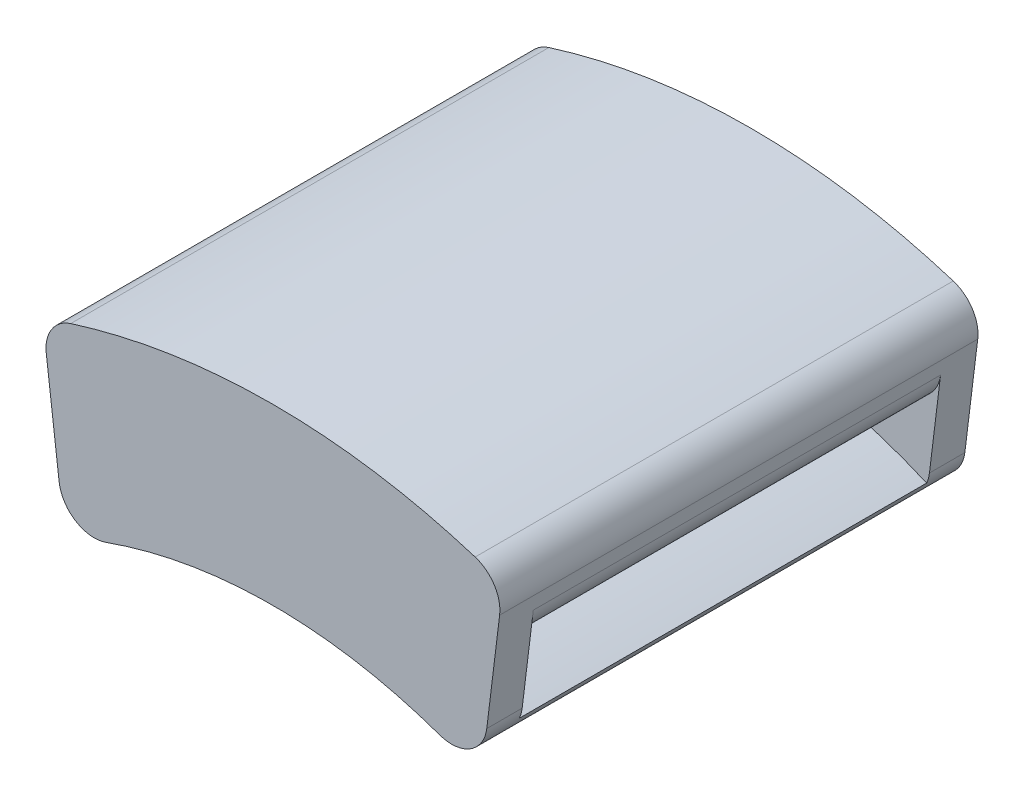
SolidWorks part; units mm, degrees
ref_plane "Front Plane" through (0, 0, 0) normal (0, 0, 1) x (1, 0, 0)
ref_plane "Top Plane" through (0, 0, 0) normal (0, 1, 0) x (1, 0, 0)
ref_plane "Right Plane" through (0, 0, 0) normal (1, 0, 0) x (0, 0, -1)
sketch "Sketch1" plane through (0, 0, 0) normal (0, 0, 1) x (1, 0, 0)
  line L0 (13.1474, 36.827) -> (12.2845, 29.8088) construction
  line L1 (-13.1588, 36.9193) -> (-12.2958, 29.9011) construction
  line L2 (-13, 35.628) -> (-12.3966, 30.7212)
  line L3 (13, 35.628) -> (12.3966, 30.7212)
  line L4 (11.7559, 25.5104) -> (12, 27.4955)
  line L5 (-10, 35.628) -> (10, 35.628) construction
  line L6 (-10, 35.628) -> (-10, 33.128) construction
  line L7 (-10, 33.128) -> (10, 33.128) construction
  line L8 (10, 35.628) -> (10, 33.128) construction
  line L9 (-11.7559, 25.5104) -> (-12, 27.4955)
  circle A0 centre (0, 0) radius 30 construction
  arc A1 (-12, 27.4955) -> (12, 27.4955) centre (0, 0) cw
  arc A2 (-13, 35.628) -> (13, 35.628) centre (0, 0) cw
  arc A3 (-12.3966, 30.7212) -> (12.3966, 30.7212) centre (0, 0) cw
  arc A4 (-11.7559, 25.5104) -> (11.7559, 25.5104) centre (0, 0) cw
  point P7 (0, 37.9257)
  point P9 (0, 30)
  point P21 (0, 33.128)
  dimension "D1" = 60
  dimension "D2" = 24
  dimension "D3" = 26
  dimension "D4" = 3.25
  dimension "D5" = 2
  dimension "D6" = 0
  dimension "D7" = 20
  dimension "D8" = 2.5
  dimension "D9" = 33.128
extrude "Boss-Extrude1" add sketch "Sketch1" along normal blind 23
ref_plane "Plane1" through (0, 32.51, 0) normal (0, 1, 0) x (1, 0, 0)
sketch "Sketch4" plane through (0, 32.51, 0) normal (0, 1, 0) x (1, 0, 0)
  line L0 (0, -23) -> (0, 0) construction
  line L1 (-13, -23) -> (13, -23) construction
  line L2 (-13, -11.5) -> (13, -11.5) construction
  line L3 (-13, -23) -> (-13, 0) construction
  line L4 (13, -23) -> (13, 0) construction
  circle A0 centre (0, -11.5) radius 10.5
  dimension "D1" = 21
extrude "Cut-Extrude1" cut sketch "Sketch4" along normal blind 2.5 and the other way up to next (2.51 mm away)
sketch "Sketch9" plane through (0, 32.51, 0) normal (0, 1, 0) x (1, 0, 0)
  circle A0 centre (0, -12) radius 7.5
  point P0 (0, -12)
  dimension "D1" = 15
sketch "Sketch7" plane through (0, 0, 0) normal (0, 0, -1) x (-1, 0, 0)
  line L0 (-13, 35.628) -> (-11.7559, 25.5104)
  line L1 (13, 35.628) -> (11.7559, 25.5104)
  arc A0 (11.7559, 25.5104) -> (-11.7559, 25.5104) centre (0, 0) ccw construction
  arc A1 (13, 35.628) -> (-13, 35.628) centre (0, 0) ccw construction
  arc A2 (11.7559, 25.5104) -> (-11.7559, 25.5104) centre (0, 0) ccw
  arc A3 (13, 35.628) -> (-13, 35.628) centre (0, 0) ccw
extrude "Boss-Extrude4" add sketch "Sketch7" along normal blind 2
sketch "Sketch8" plane through (0, 0, 23) normal (0, 0, 1) x (1, 0, 0)
  line L0 (-13, 35.628) -> (-11.7559, 25.5104)
  line L1 (11.7559, 25.5104) -> (13, 35.628)
  arc A0 (11.7559, 25.5104) -> (-11.7559, 25.5104) centre (0, 0) ccw construction
  arc A1 (13, 35.628) -> (-13, 35.628) centre (0, 0) ccw construction
  arc A2 (11.7559, 25.5104) -> (-11.7559, 25.5104) centre (0, 0) ccw
  arc A3 (13, 35.628) -> (-13, 35.628) centre (0, 0) ccw
extrude "Boss-Extrude5" add sketch "Sketch8" along normal blind 2
fillet "Fillet2" radius 2 6 edges at (12.3966, 30.7212, 11.5) (-12.3966, 30.7212, 11.5) (-13, 35.628, 11.5) (-11.7559, 25.5104, 11.5) (11.7559, 25.5104, 11.5) (13, 35.628, 11.5)
extrude "Cut-Extrude2" cut sketch "Sketch9" against normal through all
fillet "Fillet3" radius 0.9 2 edges at (-1.4315, 28.0523, 4.6379) (1.4669, 29.9641, 4.6448)
